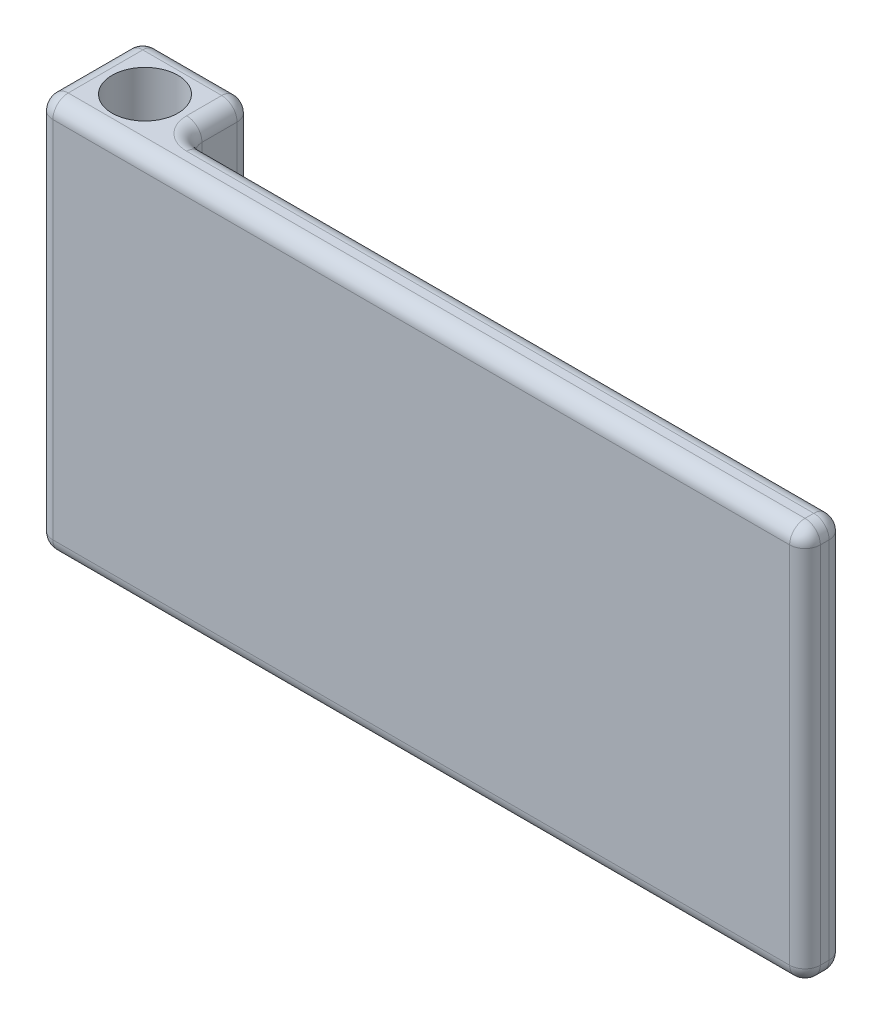
SolidWorks part; units mm, degrees
ref_plane "Plano frontal" through (0, 0, 0) normal (0, 0, 1) x (1, 0, 0)
ref_plane "Plano superior" through (0, 0, 0) normal (0, 1, 0) x (1, 0, 0)
ref_plane "Plano direito" through (0, 0, 0) normal (1, 0, 0) x (0, 0, -1)
sketch "Esboço1" plane through (0, 0, 0) normal (0, 0, 1) x (1, 0, 0)
  line L1 (0, 0) -> (175, 0)
  line L2 (0, 0) -> (0, 90)
  line L3 (0, 90) -> (175, 90)
  line L4 (175, 0) -> (175, 90)
  dimension "D1" = 175
  dimension "D2" = 90
extrude "Ressalto-extrusão1" add sketch "Esboço1" along normal blind 12 and the other way blind 12
sketch "Esboço3" plane through (0, 0, 0) normal (0, 1, 0) x (1, 0, 0)
  line L0 (175, 12) -> (0, 12) construction
  line L1 (25, 12) -> (175, 12)
  line L2 (25, 12) -> (25, -3)
  line L3 (25, -3) -> (175, -3)
  line L4 (175, 12) -> (175, -3)
  line L5 (175, 12) -> (175, -12) construction
  dimension "D1" = 150
  dimension "D2" = 15
extrude "Corte-extrusão1" cut sketch "Esboço3" against normal through all both and the other way through all
sketch "Esboço4" plane through (0, 90, 0) normal (0, 1, 0) x (1, 0, 0)
  line L0 (12.5, 12) -> (12.5, -12) construction
  line L1 (25, 12) -> (0, 12) construction
  line L2 (175, -12) -> (0, -12) construction
  circle A0 centre (12.5, 0) radius 7.5
extrude "Corte-extrusão2" cut sketch "Esboço4" against normal through all both and the other way through all
fillet "Filete1" radius 3.5 3 edges at (0, 45, -12) (25, 45, -12) (25, 45, 3)
fillet "Filete2" radius 3.5 3 edges at (87.5, 90, 12) (175, 45, 12) (175, 45, 3)
fillet "Filete3" radius 3.5 23 edges at (173.9749, 0, 10.9749) (175, 0, 7.5) (173.9749, 0, 4.0251) (0, 0, 1.75) (1.0251, 0, -10.9749) (12.5, 0, -12) (23.9749, 0, -10.9749) (25, 0, -4.5) (26.0251, 0, 1.9749) (0, 43.25, 12) (0, 88.9749, 10.9749) (0, 90, 0) (1.0251, 90, -10.9749) (12.5, 90, -12) (23.9749, 90, -10.9749) (25, 90, -4.5) (26.0251, 90, 1.9749) (173.9749, 88.9749, 10.9749) (175, 90, 7.5) (173.9749, 90, 4.0251) (85.75, 0, 12) (100, 0, 3) (100, 90, 3)
